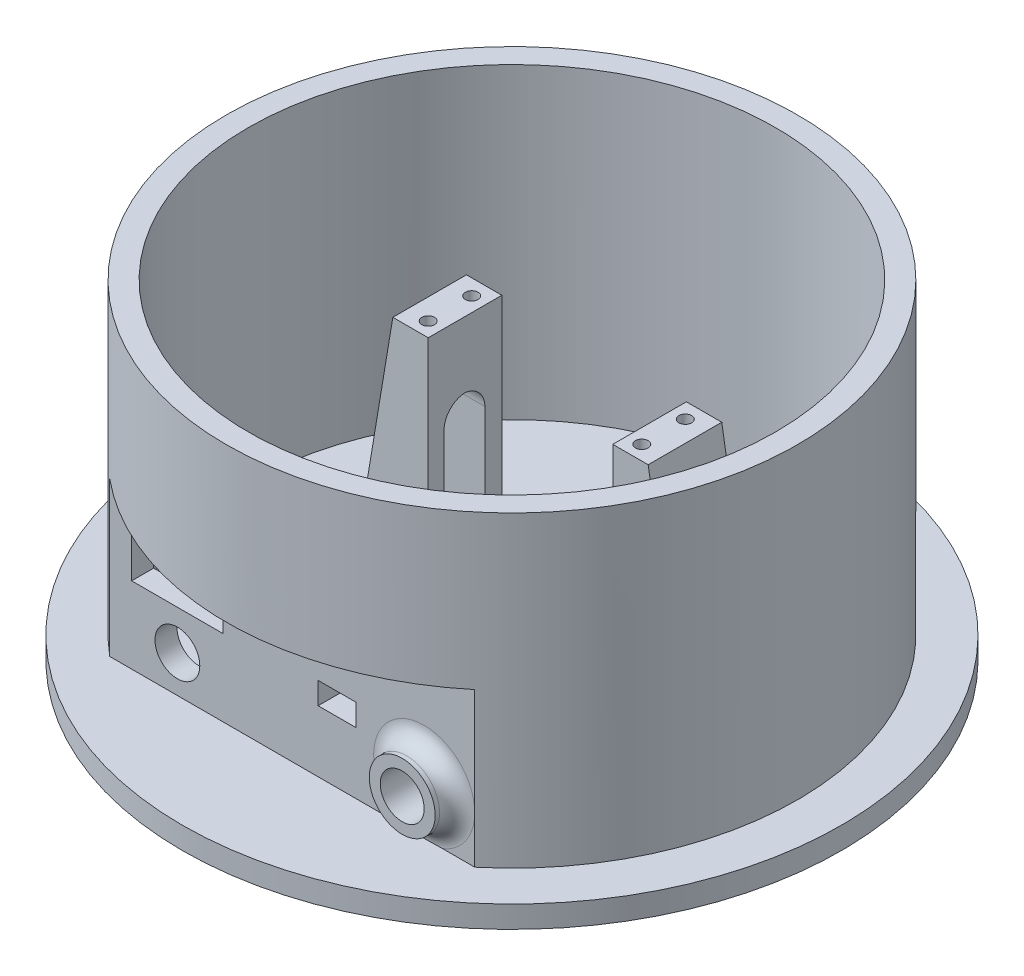
SolidWorks part; units mm, degrees
ref_plane "Front Plane" through (0, 0, 0) normal (0, 0, 1) x (1, 0, 0)
ref_plane "Top Plane" through (0, 0, 0) normal (0, 1, 0) x (1, 0, 0)
ref_plane "Right Plane" through (0, 0, 0) normal (1, 0, 0) x (0, 0, -1)
sketch "Sketch4" plane through (0, 0, 0) normal (0, 1, 0) x (1, 0, 0)
  circle A8 centre (0, 0) radius 65
  line B0 (-17.3, 2.3) -> (-17.3, 0.8)
  line B1 (-17.3, 0.75) -> (-17.3, -0.75)
  line B2 (11.8, -8.9) -> (11.8, -2)
  line B3 (11.8, 2) -> (11.8, 8.9)
  line B4 (11.8, 8.9) -> (3.9815, 8.9)
  line B5 (3.9815, -8.9) -> (11.8, -8.9)
  line B6 (24.5, -8.9) -> (3.9815, -8.9)
  line B7 (0, -9.75) -> (29.7, -9.75)
  line B8 (29.7, -9.75) -> (29.7, 9.75)
  line B9 (29.7, 9.75) -> (0, 9.75)
  line B10 (3.9815, 8.9) -> (24.5, 8.9)
  line B11 (23.4, -7.85) -> (23.4, 7.85)
  line B12 (23.4, 7.85) -> (12.9, 7.85)
  line B13 (12.9, 7.85) -> (12.9, -7.85)
  line B14 (12.9, -7.85) -> (23.4, -7.85)
  line B15 (24.5, -8.9) -> (24.5, 8.9)
  line B16 (11.8, 8.9) -> (11.8, -8.9)
  line B17 (11.8, -8.9) -> (24.5, -8.9)
  line B18 (-9.8, 0.5) -> (-16.8, 0.5)
  line B19 (-16.8, -0.5) -> (-9.8, -0.5)
  line B20 (-9.8, -0.5) -> (-9.8, 0.5)
  line B21 (-16.8, -0.5) -> (-16.8, -3.45)
  line B22 (-15.3, -9.25) -> (-9.8, -9.25)
  line B23 (-9.8, -9.25) -> (-9.8, -0.5)
  line B24 (-9.8, 0.5) -> (-9.8, 9.25)
  line B25 (-9.8, 9.25) -> (-15.3, 9.25)
  line B26 (-16.8, 7.75) -> (-16.8, 6.45)
  line B27 (-15.8321, 3.95) -> (-16.3, 3.95)
  line B28 (-16.8, 3.45) -> (-16.8, 0.5)
  line B29 (37.2, 0.5) -> (30.2, 0.5)
  line B30 (30.2, 0.5) -> (30.2, -0.5)
  line B31 (30.2, -0.5) -> (37.2, -0.5)
  line B32 (-9.8, -9.25) -> (-9.8, -0.5)
  line B33 (30.2, -0.5) -> (30.2, -9.25)
  line B34 (30.2, -9.25) -> (35.7, -9.25)
  line B35 (37.2, -7.75) -> (37.2, -6.45)
  line B36 (36.7, -5.95) -> (36.2321, -5.95)
  line B37 (37.2, -3.45) -> (37.2, -0.5)
  line B38 (30.2, 9.25) -> (30.2, 0.5)
  line B39 (30.2, 0.5) -> (37.2, 0.5)
  line B40 (37.2, 0.5) -> (37.2, 3.45)
  line B41 (37.2, 6.45) -> (37.2, 7.75)
  line B42 (35.7, 9.25) -> (30.2, 9.25)
  line B43 (-9.8, 9.5) -> (-9.8, -9.5)
  line B44 (-9.3, -10) -> (29.7, -10)
  line B45 (30.2, -9.5) -> (30.2, 9.5)
  line B46 (29.7, 10) -> (-9.3, 10)
  line B47 (0, 9.75) -> (-9.3, 9.75)
  line B48 (-9.3, 9.75) -> (-9.3, 2.9279)
  line B49 (-9.3, -2.9279) -> (-9.3, -9.75)
  line B50 (-9.3, -9.75) -> (0, -9.75)
  line B51 (-14.3, 2.921) -> (-10.3, 3.2007)
  line B52 (-10.3, 3.5) -> (-14.3, 3.2203)
  line B53 (-14.3, -3.2203) -> (-10.3, -3.5)
  line B54 (-10.3, -3.2007) -> (-14.3, -2.921)
  line B55 (-9.8, -10.25) -> (30.2, -10.25)
  line B56 (29.7, -10) -> (-9.3, -10)
  line B57 (30.2, 10.25) -> (-9.8, 10.25)
  line B58 (-9.3, 10) -> (29.7, 10)
  line B59 (-17.3, 2.3) -> (-17.3, -2.301)
  circle B60 centre (0, 0) radius 5.3
  arc B61 (11.8, 2) -> (11.8, -2) centre (11.8, 0) ccw
  arc B62 (3.9815, 8.9) -> (3.9815, -8.9) centre (0, 0) ccw
  arc B63 (24.5, -5.1324) -> (24.5, 5.1324) centre (20.8069, 0) ccw
  arc B64 (-15.8321, -5.95) -> (-15.8321, -3.95) centre (-14.1, -4.95) ccw
  arc B65 (-15.3, 9.25) -> (-16.8, 7.75) centre (-15.3, 7.75) ccw
  arc B66 (-15.8321, 3.95) -> (-15.8321, 5.95) centre (-14.1, 4.95) ccw
  circle B67 centre (0, 0) radius 3
  circle B68 centre (0, 0) radius 6.5
  arc B69 (-15.8321, 3.95) -> (-15.8321, 5.95) centre (-14.1, 4.95) ccw
  arc B70 (36.2321, -3.95) -> (36.2321, -5.95) centre (34.5, -4.95) ccw
  arc B71 (37.2, 3.45) -> (36.7, 3.95) centre (36.7, 3.45) ccw
  arc B72 (36.2321, 5.95) -> (36.2321, 3.95) centre (34.5, 4.95) ccw
  arc B73 (37.2, 7.75) -> (35.7, 9.25) centre (35.7, 7.75) ccw
  arc B74 (0, 9.75) -> (-9.3, 2.9279) centre (0, 0) ccw
  dimension "D1" = 130
sketch_block_instance "MG996R_TOP-2"
sketch_block "MG996R_TOP"
extrude "Extrude-Thin1" add sketch "Sketch4" along normal blind 75 thin thin type one direction reverse wall 5
sketch "Sketch5" plane through (0, 0, 0) normal (0, 1, 0) x (1, 0, 0)
  circle A0 centre (0, 0) radius 65 construction
  circle A1 centre (0, 0) radius 65 construction
  circle A2 centre (0, 0) radius 75
  dimension "D1" = 10
extrude "Boss-Extrude1" add sketch "Sketch5" along normal blind 5 contours A2
ref_plane "Plane1" through (0, 45, 0) normal (0, 1, 0) x (1, 0, 0)
sketch "Sketch6" plane through (0, 45, 0) normal (0, 1, 0) x (1, 0, 0)
  line L0 (0, -50) -> (0, -65) construction
  line L1 (-41.5331, -50) -> (41.5331, -50)
  line L6 (-41.5331, -50) -> (41.5331, -50)
  line L7 (-41.5331, -50) -> (-41.5331, -45)
  line L8 (-41.5331, -45) -> (41.5331, -45)
  line L9 (41.5331, -50) -> (41.5331, -45)
  circle A0 centre (0, 0) radius 65 construction
  arc A1 (-41.5331, -50) -> (41.5331, -50) centre (0, 0) ccw
  point P9 (0, -50)
  dimension "D2" = 5
  dimension "D1" = 15
extrude "Boss-Extrude2" add sketch "Sketch6" against normal up to surface (40 mm away) contours L1 L6 L9 L8 L7 | L6 L0 A1 | L0 L1 A1 region at (15.8461, 45, 56.0636) region at (-15.8461, 45, 56.0636) region at (0, 45, 47.5) up to face at (0, 5, 65)
sketch "Sketch7" plane through (0, 45, 0) normal (0, 1, 0) x (1, 0, 0)
  line L0 (-39.6863, -45) -> (39.6863, -45) construction
  line L1 (-46.9042, -45) -> (46.9042, -45) construction
  line L2 (-41.5331, -50) -> (41.5331, -50)
  line L3 (-46.9042, -50) -> (46.9042, -50) construction
  circle A0 centre (0, 0) radius 65 construction
  arc A1 (-41.5331, -50) -> (41.5331, -50) centre (0, 0) ccw
  dimension "D1" = 5
extrude "Cut-Extrude1" cut sketch "Sketch7" against normal up to surface (40 mm away) from offset 5 up to face at (0, 5, 65) offset against normal yes
sketch "Sketch8" plane through (0, 5, 0) normal (0, 1, 0) x (1, 0, 0)
  line L0 (31.2, -8.25) -> (31.2, 8.5)
  line L1 (31.2, 8.5) -> (38.8, 8.5)
  line L2 (37.8, -8.25) -> (37.8, 8.5) construction
  line L3 (31.2, -8.25) -> (38.8, -8.25)
  line L4 (-10.8, -8.25) -> (-10.8, 8.5)
  line L5 (-10.8, 8.5) -> (-18.4, 8.5)
  line L6 (-17.4, -8.25) -> (-17.4, 8.5) construction
  line L9 (-10.8, -8.25) -> (-18.4, -8.25)
  line L10 (-14.1, 4.95) -> (-14.1, -4.95) construction
  line L14 (34.5, 4.95) -> (34.5, -4.95) construction
  line L15 (30.2, 9.5) -> (38.8, 9.5) construction
  line L16 (38.8, -9.25) -> (38.8, 9.5) construction
  line L17 (-10.8, 8.5) -> (-17.4, 8.5) construction
  line L19 (-9.8, -9.25) -> (-18.4, -9.25) construction
  line L21 (-9.8, -9.25) -> (-9.8, 9.5) construction
  line L22 (-9.8, -0.5) -> (30.2, -0.5) construction
  line L23 (-9.8, 9.5) -> (-18.4, 9.5) construction
  line L24 (-18.4, -9.25) -> (-18.4, 9.5) construction
  line L25 (10.2, -0.5) -> (10.2, -3.95) construction
  line L26 (30.2, -9.25) -> (38.8, -9.25) construction
  line L27 (30.2, -9.25) -> (30.2, 9.5) construction
  line L28 (-10.8, -8.25) -> (-17.4, -8.25) construction
  line L29 (31.2, 8.5) -> (37.8, 8.5) construction
  line L30 (31.2, -8.25) -> (37.8, -8.25) construction
  line L31 (-18.4, 8.5) -> (-18.4, -8.25)
  line L32 (38.8, 8.5) -> (38.8, -8.25)
  arc A0 (-15.8321, 3.95) -> (-15.8321, 5.95) centre (-14.1, 4.95) ccw construction
  arc A1 (-15.8321, -5.95) -> (-15.8321, -3.95) centre (-14.1, -4.95) ccw construction
  circle A4 centre (-14.1, 4.95) radius 2
  circle A5 centre (-14.1, -4.95) radius 2
  circle A6 centre (34.5, 4.95) radius 2
  circle A8 centre (34.5, -4.95) radius 2
  point P0 (-14.1, -4.95)
  point P2 (-14.1, 4.95)
  dimension "D1" = 1
  dimension "D2" = 1
extrude "Boss-Extrude3" add sketch "Sketch8" along normal offset from surface (57.3 mm away) 12.7 contours L0 L3 L2 L1 A6 A8 | A6 | A8 | A5 | L9 L4 L5 L6 A5 A4 | A4 | A8 | A6 | L0 L1 L32 L3 region at (35.123, 5, -0.1557) region at (-14.723, 5, -0.1557) region at (-14.1, 5, -4.95) region at (-14.1, 5, 4.95) region at (34.5, 5, -4.95) region at (34.5, 5, 4.95) up to face at (0, 75, 65)
chamfer "Chamfer1" distance 10 distance2 60 2 edges at (38.8, 5, -0.125) (-18.4, 5, -0.125) first distance on face at (0, 5, -7.5)
sketch "Sketch9" plane through (0, 62.3, 0) normal (0, 1, 0) x (1, 0, 0)
  point P0 (34.5, 4.95)
  point P1 (34.5, -4.95)
  point P3 (-14.1, 4.95)
  point P5 (-14.1, -4.95)
hole_wizard "M3.5x0.6 Tapped Hole1" positions "Sketch9" profile "Sketch10" tap size "M3.5x0.6" standard "ANSI Metric"
sketch "Sketch10" plane through (34.5, 62.3, -4.95) normal (1, 0, 0) x (0, 0, 1)
  line L0 (0, 0) -> (0, 10)
  line L1 (0, 10) -> (1.45, 9.1288)
  line L2 (1.45, 9.1288) -> (1.45, 0)
  line L5 (1.45, 0) -> (0, 0)
  line L10 (0, 10) -> (-1.45, 9.1288) construction
  line L11 (0, -6.35) -> (0, 107.95) construction
  dimension "Tap Drill Dia." = 2.9
  dimension "Tap Drill Depth" = 10
  dimension "Drill Angle" = 118
cosmetic thread "Hole Thread1" parameters "D1"=7, "D2"=3.5
cosmetic thread "Hole Thread2" parameters "D1"=7, "D2"=3.5
cosmetic thread "Hole Thread3" parameters "D1"=7, "D2"=3.5
cosmetic thread "Hole Thread4" parameters "D1"=7, "D2"=3.5
sketch "Sketch11" plane through (0, 62.3, 0) normal (0, 1, 0) x (1, 0, 0)
  line L0 (-9.777, 4.6395) -> (-28.4, 4.6395)
  line L1 (-28.4, -8.25) -> (-28.4, 8.5) construction
  line L2 (-28.4, 4.6395) -> (-28.4, -4.6395)
  line L3 (-28.4, -4.6395) -> (-9.777, -4.6395)
  line L4 (0, 0) -> (-37.1678, 0) construction
  line L5 (-9.777, 4.6395) -> (-9.777, -4.6395)
extrude "Cut-Extrude2" cut sketch "Sketch11" along normal offset from surface (42.3 mm away) 15 from surface up to face at (-14.1, 62.3, -3.5) starting at face at (0, 5, -7.5)
fillet "Fillet1" radius 5 2 edges at (-16.075, 47.3, -4.6395) (-16.075, 47.3, 4.6395)
sketch "Sketch12" plane through (0, 0, 50) normal (0, 0, 1) x (1, 0, 0)
  line L0 (-36.5331, 22.4) -> (-15.7331, 22.4)
  line L1 (-36.5331, 22.4) -> (-36.5331, 35)
  line L2 (-36.5331, 35) -> (-15.7331, 35)
  line L3 (-15.7331, 22.4) -> (-15.7331, 35)
  line L4 (-36.5331, 35) -> (-15.7331, 22.4) construction
  line L5 (-41.5331, 40) -> (41.5331, 40) construction
  line L6 (-41.5331, 5) -> (-41.5331, 40) construction
  line L7 (-26.1331, 7.55) -> (-26.1331, 49.85) construction
  line L8 (-26.1331, 7.55) -> (-26.1331, 19.25)
  line L9 (6.4, 19.5) -> (14, 19.5) construction
  line L10 (6.4, 19.5) -> (6.4, 23.5) construction
  line L11 (6.4, 23.5) -> (14, 23.5) construction
  line L12 (14, 19.5) -> (14, 23.5) construction
  line L13 (6.4, 19.5) -> (14, 23.5) construction
  line L14 (6.4, 23.5) -> (14, 19.5) construction
  line L15 (-41.5331, 5) -> (41.5331, 5) construction
  line L16 (14.5, 19) -> (14.5, 24)
  line L17 (5.9, 24) -> (14.5, 24)
  line L18 (5.9, 19) -> (5.9, 24)
  line L19 (5.9, 19) -> (14.5, 19)
  circle A0 centre (-26.1331, 13.4) radius 5.1
  point P8 (-26.1331, 7.55)
  point P14 (-26.1331, 13.4)
  point P16 (-26.1331, 28.7)
  point P17 (10.2, 21.5)
  dimension "D6" = 10.2
  dimension "D7" = 9
  dimension "D1" = 20.8
  dimension "D2" = 12.6
  dimension "D3" = 5
  dimension "D4" = 5
  dimension "D5" = 11.7
  dimension "D8" = 4
  dimension "D9" = 7.6
  dimension "D10" = 14.5
  dimension "D11" = 0.5
extrude "Cut-Extrude3" cut sketch "Sketch12" against normal up to next contours L3 L2 L1 L0 | A0 | L16 L17 L18 L19
sketch "Sketch13" plane through (0, 0, 50) normal (0, 0, 1) x (1, 0, 0)
  line L0 (41.5331, 5) -> (41.5331, 40) construction
  circle A0 centre (30.0331, 15.716) radius 7.5
  circle A1 centre (30.0331, 15.716) radius 5
  point P4 (37.5331, 15.716)
  dimension "D1" = 15
  dimension "D2" = 10
  dimension "D3" = 4
extrude "Boss-Extrude4" add sketch "Sketch13" along normal blind 5
fillet "Fillet2" radius 4 1 edges at (22.5331, 15.716, 50)
sketch "Sketch14" plane through (0, 0, 50) normal (0, 0, 1) x (1, 0, 0)
  circle A1 centre (30.0331, 15.716) radius 5
  circle A2 centre (30.0331, 15.716) radius 5
  dimension "D1" = 0
extrude "Cut-Extrude4" cut sketch "Sketch14" against normal up to next
